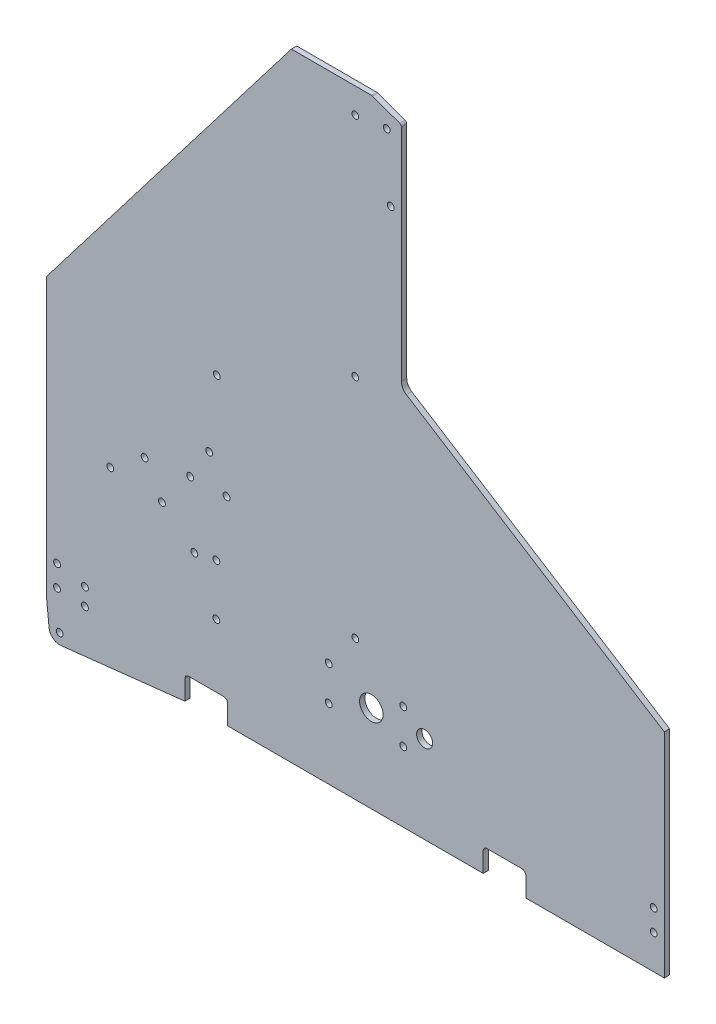
SolidWorks part; units mm, degrees
ref_plane "Front Plane" through (0, 0, 0) normal (0, 0, 1) x (1, 0, 0)
ref_plane "Top Plane" through (0, 0, 0) normal (0, 1, 0) x (1, 0, 0)
ref_plane "Right Plane" through (0, 0, 0) normal (1, 0, 0) x (0, 0, -1)
sketch "Sketch1" plane through (0, 0, 0) normal (0, 0, 1) x (1, 0, 0)
  line L0 (82.55, -20.32) -> (82.55, -6.35)
  line L2 (0, 0) -> (0, 157.48)
  line L4 (368.3, -20.32) -> (368.3, 106.68)
  line L5 (82.55, -6.35) -> (107.95, -6.35)
  line L6 (107.95, -6.35) -> (107.95, -20.32)
  line L7 (107.95, -20.32) -> (260.35, -20.32)
  line L8 (260.35, -20.32) -> (260.35, -6.35)
  line L9 (260.35, -6.35) -> (285.75, -6.35)
  line L10 (285.75, -6.35) -> (285.75, -20.32)
  line L11 (285.75, -20.32) -> (368.3, -20.32)
  line L12 (361.95, 12.7) -> (368.3, 12.7) construction
  line L13 (0, 0) -> (6.35, 0) construction
  line L14 (0.0315, -6.9818) -> (1.619, -22.8568)
  line L15 (8.6391, -28.5361) -> (82.55, -20.32)
  line L16 (0, 0) -> (0, -6.35)
  line L17 (85.725, 97.155) -> (82.9754, 95.5675) construction
  line L18 (97.0634, 115.6163) -> (58.5686, 93.3913) construction
  line L19 (97.0634, 115.6163) -> (107.3822, 97.7437) construction
  line L20 (58.5686, 93.3913) -> (68.8873, 75.5187) construction
  line L21 (107.3822, 97.7437) -> (68.8873, 75.5187) construction
  line L22 (97.0634, 115.6163) -> (68.8873, 75.5187) construction
  line L23 (58.5686, 93.3913) -> (107.3822, 97.7437) construction
  line L24 (7.9375, -22.225) -> (88.2169, 59.1366) construction
  line L25 (184.15, 62.98) -> (184.15, 197.98) construction
  line L26 (184.15, 197.98) -> (184.15, 332.98) construction
  line L27 (355.6, 335.28) -> (330.2, 335.28) construction
  line L28 (330.2, 335.28) -> (330.2, 220.98) construction
  line L29 (330.2, 220.98) -> (355.6, 220.98) construction
  line L30 (355.6, 220.98) -> (355.6, 335.28) construction
  line L31 (184.15, 347.98) -> (184.15, 269.4703) construction
  line L32 (12.7, 335.28) -> (38.1, 335.28) construction
  line L33 (38.1, 335.28) -> (38.1, 220.98) construction
  line L34 (12.7, 220.98) -> (12.7, 335.28) construction
  line L35 (38.1, 220.98) -> (12.7, 220.98) construction
  line L36 (194.15, 347.98) -> (211.6138, 341.63)
  line L37 (184.15, 347.98) -> (146.05, 347.98)
  line L38 (184.15, 347.98) -> (194.15, 347.98)
  line L39 (348.5362, 347.98) -> (413.4623, 347.98)
  line L40 (348.5362, 347.98) -> (211.6138, 347.98) construction
  line L42 (146.05, 347.98) -> (0, 157.48)
  line L44 (211.6138, 341.63) -> (211.6138, 205.74)
  line L45 (211.6138, 205.74) -> (368.3, 106.68)
  line L46 (194.15, 347.98) -> (-141.0713, 347.98) construction
  circle A0 centre (6.35, 0) radius 2.032
  circle A1 centre (6.35, 12.7) radius 2.032
  circle A2 centre (361.95, 0) radius 2.032
  circle A3 centre (361.95, 12.7) radius 2.032
  arc A5 (1.619, -22.8568) -> (8.6391, -28.5361) centre (7.9375, -22.225) ccw
  circle A6 centre (7.9375, -22.225) radius 2.032
  arc A7 (0, -6.35) -> (0.0315, -6.9818) centre (6.35, -6.35) ccw
  circle A8 centre (38.1, 78.105) radius 2.032
  circle A9 centre (85.725, 97.155) radius 2.032
  circle A10 centre (58.5686, 93.3913) radius 2.032
  circle A11 centre (68.8873, 75.5187) radius 2.032
  circle A12 centre (107.3822, 97.7437) radius 2.032
  circle A13 centre (97.0634, 115.6163) radius 2.032
  circle A14 centre (88.2169, 59.1366) radius 2.032
  circle A15 centre (184.15, 62.98) radius 2
  circle A16 centre (184.15, 197.98) radius 2
  circle A17 centre (184.15, 332.98) radius 2
  circle A18 centre (63.5, 316.23) radius 2.032
  circle A19 centre (101.6, 157.48) radius 2.032
  circle A20 centre (355.6, 335.28) radius 2.032
  circle A21 centre (330.2, 335.28) radius 2.032
  circle A22 centre (355.6, 220.98) radius 2.032
  circle A23 centre (330.2, 220.98) radius 2.032
  circle A24 centre (12.7, 335.28) radius 2.032
  circle A25 centre (38.1, 335.28) radius 2.032
  circle A26 centre (12.7, 220.98) radius 2.032
  circle A27 centre (38.1, 220.98) radius 2.032
  circle A28 centre (202.8819, 335.28) radius 2
  circle A29 centre (205.2638, 296.418) radius 2.032
  point P82 (184.15, 347.98)
  point P83 (202.8819, 344.805)
  dimension "D6" = 4.064
  dimension "D10" = 6.35
  dimension "D11" = 4.064
  dimension "D17" = 38.1
  dimension "D27" = 4
  dimension "D31" = 4.064
  dimension "D32" = 38.1
  dimension "D36" = 4.064
  dimension "D47" = 45.212
  dimension "D48" = 4.064
  dimension "D2" = 127
  dimension "D3" = 13.97
  dimension "D4" = 25.4
  dimension "D5" = 152.4
  dimension "D7" = 12.7
  dimension "D8" = 6.35
  dimension "D9" = 20.32
  dimension "D12" = 22.225
  dimension "D13" = 1.5875
  dimension "D14" = 82.55
  dimension "D15" = 368.3
  dimension "D16" = 6.35
  dimension "D18" = 98.425
  dimension "D19" = 47.625
  dimension "D20" = 19.05
  dimension "D21" = 3.175
  dimension "D22" = 60
  dimension "D23" = 20.6375
  dimension "D24" = 44.45
  dimension "D25" = 38.1
  dimension "D26" = 114.3
  dimension "D28" = 135
  dimension "D29" = 12.7
  dimension "D30" = 15
  dimension "D33" = 63.5
  dimension "D34" = 27.4638
  dimension "D35" = 101.6
  dimension "D37" = 114.3
  dimension "D38" = 25.4
  dimension "D39" = 12.7
  dimension "D40" = 157.48
  dimension "D41" = 142.24
  dimension "D42" = 368.3
  dimension "D43" = 10
  dimension "D44" = 6.35
  dimension "D45" = 31.75
  dimension "D46" = 6.35
  dimension "D49" = 6.35
extrude "Boss-Extrude1" add sketch "Sketch1" along normal blind 3.175 contours L16 A7 L14 A5 L15 L0 L5 L6 L7 L8 L9 L10 L11 L4 L42 L2 A19 A17 A16 A15 A14 A13 A12 A11 A10 A9 A8 A0 A1 A2 A3 A6 region at (167.243, 117.6611, 0)
fillet "Fillet1" radius 2.286 4 edges at (285.75, -6.35, 1.5875) (107.95, -6.35, 1.5875) (260.35, -6.35, 1.5875) (82.55, -6.35, 1.5875)
fillet "Fillet2" radius 6.35 1 edges at (211.6138, 205.74, 1.5875)
sketch "Sketch2" plane through (0, 0, 0) normal (0, 0, -1) x (-1, 0, 0)
  circle A0 centre (-101.3398, 61.8475) radius 2.032 construction
  circle A1 centre (-101.3398, 31.3675) radius 2.032 construction
  circle A2 centre (-23.012, 8.964) radius 2.032 construction
  circle A3 centre (-23.012, -1.196) radius 2.032 construction
  circle A4 centre (-101.3398, 61.8475) radius 2.032
  circle A5 centre (-101.3398, 31.3675) radius 2.032
  circle A6 centre (-23.012, 8.964) radius 2.032
  circle A7 centre (-23.012, -1.196) radius 2.032
extrude "Cut-Extrude1" cut sketch "Sketch2" against normal through all
fillet "Fillet3" radius 1.5875 2 edges at (211.6138, 341.63, 1.5875) (194.15, 347.98, 1.5875)
sketch "Sketch3" plane through (0, 0, 3.175) normal (0, 0, 1) x (1, 0, 0)
  line L0 (168.275, 42.0688) -> (212.725, 42.0688) construction
  line L1 (168.275, 42.0688) -> (168.275, 21.4313) construction
  line L2 (212.725, 42.0688) -> (212.725, 21.4313) construction
  line L3 (168.275, 21.4313) -> (212.725, 21.4313) construction
  line L4 (168.275, 42.0688) -> (212.725, 21.4313) construction
  line L5 (212.725, 42.0688) -> (168.275, 21.4313) construction
  line L6 (193.675, 31.75) -> (190.5, 31.75) construction
  line L7 (260.35, -20.32) -> (260.35, -6.35) construction
  line L8 (260.35, -6.35) -> (285.75, -6.35) construction
  circle A0 centre (193.675, 31.75) radius 6.985
  circle A1 centre (212.725, 42.0688) radius 2.032
  circle A2 centre (212.725, 21.4313) radius 2.032
  circle A3 centre (168.275, 21.4313) radius 2.032
  circle A4 centre (168.275, 42.0688) radius 2.032
  circle A5 centre (225.425, 31.75) radius 4.7625
  point P1 (190.5, 31.75)
  point P16 (0, 0)
  point P19 (0, 0)
  dimension "D4" = 13.97
  dimension "D5" = 4.064
  dimension "D8" = 9.525
  dimension "D1" = 44.45
  dimension "D2" = 20.6375
  dimension "D3" = 3.175
  dimension "D6" = 66.675
  dimension "D7" = 38.1
  dimension "D9" = 31.75
extrude "Cut-Extrude2" cut sketch "Sketch3" against normal through all
